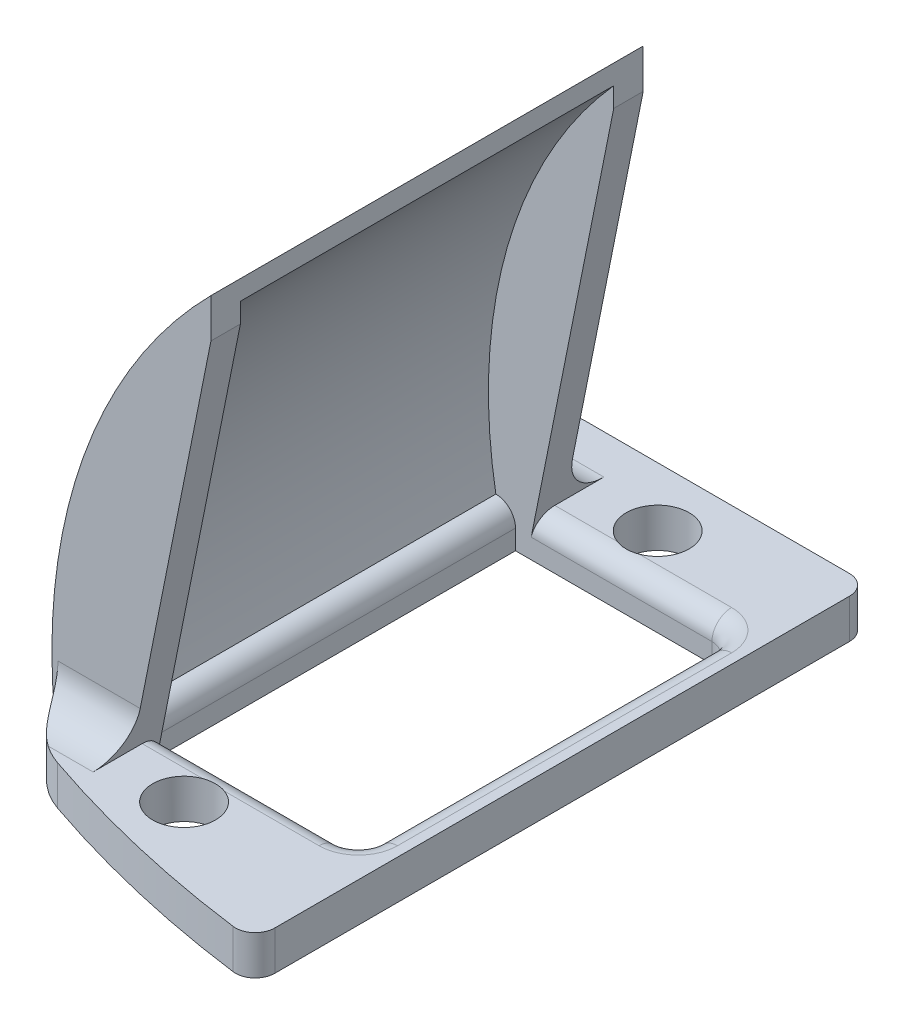
SolidWorks part; units mm, degrees
ref_plane "Front" through (0, 0, 0) normal (0, 0, 1) x (1, 0, 0)
ref_plane "Top" through (0, 0, 0) normal (0, 1, 0) x (1, 0, 0)
ref_plane "Right" through (0, 0, 0) normal (1, 0, 0) x (0, 0, -1)
sketch "Sketch1" plane through (0, 0, 0) normal (0, 1, 0) x (1, 0, 0)
  line L0 (8.4951, 30.5645) -> (8.4951, 0.3942) construction
  line L2 (-0.0049, 3.0645) -> (-0.0049, 30.5645)
  line L3 (-0.0049, 30.5645) -> (15.4951, 30.5645)
  line L4 (15.4951, -0.8135) -> (15.4951, 30.5645)
  line L5 (2.9951, 25.0645) -> (13.9951, 25.0645)
  line L6 (2.9951, 25.0645) -> (2.9951, 6.0645)
  line L7 (2.9951, 6.0645) -> (13.9951, 6.0645)
  line L8 (13.9951, 25.0645) -> (13.9951, 6.0645)
  arc A0 (-0.0049, 3.0645) -> (15.4951, -0.8135) centre (22.1784, 58.8131) ccw
  point P12 (8.4951, 25.0645)
  point P13 (8.4951, 27.5645)
  point P16 (8.4951, 3.5645)
  dimension "D9" = 60
  dimension "D1" = 1.5
  dimension "D2" = 5.5
  dimension "D3" = 11
  dimension "D4" = 19
  dimension "D5" = 3
  dimension "D6" = 27.5
  dimension "D7" = 3.0645
  dimension "D8" = 15.4951
  dimension "D10" = 31.3781
  dimension "D11" = 2.5
  dimension "D12" = 2.5
extrude "Boss-Extrude1" add sketch "Sketch1" along normal blind 2
ref_plane "Plane1" through (0, 0, -15.5645) normal (0, 0, 1) x (1, 0, 0)
sketch "Sketch2" plane through (0, 0, -15.5645) normal (0, 0, 1) x (1, 0, 0)
  line L0 (-0.0049, 2) -> (-0.0049, 0) construction
  line L1 (15.4951, 2) -> (-0.0049, 2) construction
  line L2 (7.9951, 24) -> (7.9951, 2) construction
  line L3 (7.9951, 24) -> (7.9951, 23)
  line L4 (-0.0049, 2) -> (1.9951, 2)
  arc A0 (-0.0049, 2) -> (7.9951, 24) centre (27.8999, 4.3074) cw
  arc A1 (7.9951, 23) -> (1.9951, 2) centre (26.6187, 6.3218) ccw
  dimension "D2" = 28
  dimension "D5" = 22
  dimension "D6" = 25
  dimension "D1" = 8
  dimension "D3" = 1
  dimension "D4" = 2
extrude "Boss-Extrude2" add sketch "Sketch2" along normal blind 11 and the other way blind 11
sketch "Sketch3" plane through (0, 0, -4.5645) normal (0, 0, 1) x (1, 0, 0)
  line L0 (7.9951, 24) -> (7.9951, 22)
  line L1 (7.9951, 23) -> (7.9951, 24) construction
  line L2 (7.9951, 22) -> (3.9951, 2)
  line L3 (15.4951, 2) -> (-0.0049, 2) construction
  line L4 (-0.0049, 2) -> (3.9951, 2)
  arc A0 (7.9951, 24) -> (-0.0049, 2) centre (27.8999, 4.3074) ccw construction
  arc A1 (-0.0049, 2) -> (7.9951, 24) centre (29.9545, 3.5602) cw
  dimension "D2" = 30
  dimension "D1" = 4
  dimension "D3" = 2
extrude "Boss-Extrude3" add sketch "Sketch3" against normal blind 1.5
extrude "Boss-Extrude4" add sketch "Sketch3<2>" along normal blind 1.5 from surface starting at face at (3.2891, 13.1415, -26.5645)
sketch "Sketch3<2>" plane through (0, 0, -4.5645) normal (0, 0, 1) x (1, 0, 0) same geometry as "Sketch3"
sketch "Sketch4" plane through (0, 2, 0) normal (0, 1, 0) x (1, 0, 0)
  line L0 (7.7451, 30.5645) -> (7.6154, 0.6073) construction
  line L1 (15.4951, 30.5645) -> (-0.0049, 30.5645) construction
  line L2 (3.9951, 6.0645) -> (13.9951, 6.0645) construction
  line L3 (13.9951, 25.0645) -> (3.9951, 25.0645) construction
  arc A0 (-0.0049, 3.0645) -> (15.4951, -0.8135) centre (22.1784, 58.8131) ccw construction
  circle A1 centre (7.7321, 27.5645) radius 1.6
  circle A2 centre (7.6282, 3.5645) radius 1.6
  point P7 (7.7321, 27.5645)
  point P8 (7.6282, 3.5645)
  dimension "D3" = 3.2
  dimension "D4" = 3.2
  dimension "D1" = 2.5
  dimension "D2" = 2.5
extrude "Cut-Extrude1" cut sketch "Sketch4" against normal through all
fillet "Fillet1" radius 4 1 edges at (-0.0049, 1, -3.0645)
fillet "Fillet2" radius 1 9 edges at (8.9951, 2, -6.0645) (13.9951, 1, -6.0645) (2.9951, 2, -15.5645) (13.9951, 1, -25.0645) (8.9951, 2, -25.0645) (13.9951, 2, -15.5645) (-0.0049, 1, -30.5645) (15.4951, 1, -30.5645) (15.4951, 1, 0.8135)
fillet "Fillet3" radius 2 2 edges at (1.9951, 2, -26.5645) (2.1007, 2, -4.5645)
